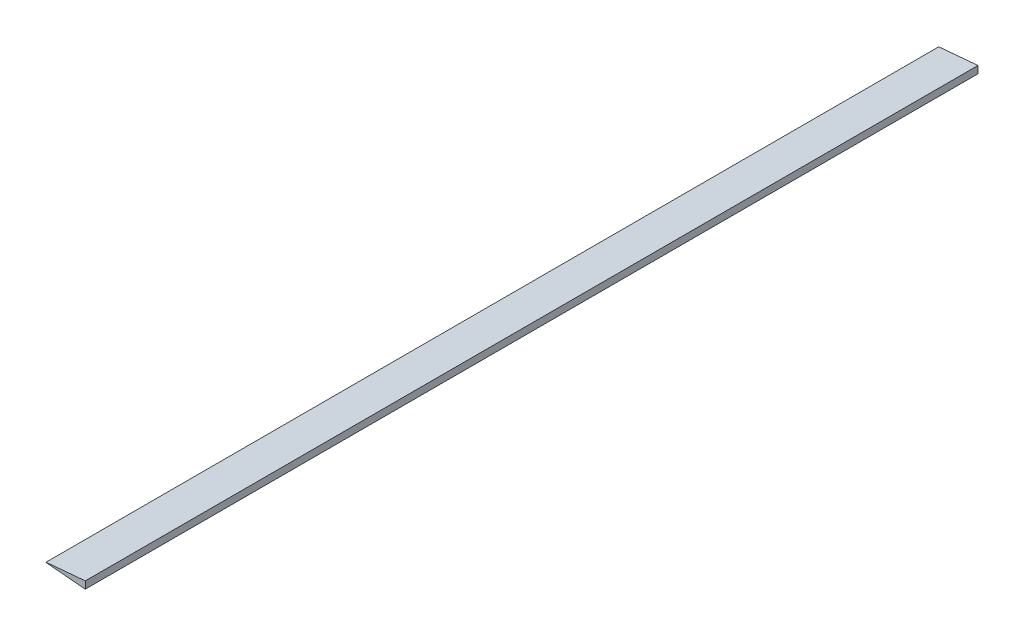
SolidWorks part; units mm, degrees
ref_plane "Front Plane" through (0, 0, 0) normal (0, 0, 1) x (1, 0, 0)
ref_plane "Top Plane" through (0, 0, 0) normal (0, 1, 0) x (1, 0, 0)
ref_plane "Right Plane" through (0, 0, 0) normal (1, 0, 0) x (0, 0, -1)
sketch "Sketch1" plane through (0, 0, 0) normal (0, 0, 1) x (1, 0, 0)
  line L0 (-86.8182, 3.4071) -> (-86.8182, -3.4071)
  line L1 (-124.026, 0.1172) -> (-124.026, -0.1172)
  spline S0 degree 3 poles (-86.8182, 3.4071) (-86.9575, 3.3973) (-89.0253, 3.2514) (-92.9071, 2.9508) (-98.3311, 2.5177) (-103.3571, 2.0925) (-107.93, 1.6883) (-111.9999, 1.3136) (-115.5222, 0.9774) (-118.4581, 0.6885) (-120.7757, 0.4545) (-122.4494, 0.2821) (-123.4611, 0.1766) (-123.9128, 0.1291) (-124.026, 0.1172) knots 0 0 0 0 0.011212 0.166483 0.312686 0.448211 0.571563 0.681381 0.776452 0.855723 0.918312 0.963525 0.990856 1 1 1 1
  spline S1 degree 3 poles (-86.8182, -3.4071) (-86.9575, -3.3973) (-89.0253, -3.2514) (-92.9071, -2.9508) (-98.3311, -2.5177) (-103.3571, -2.0925) (-107.93, -1.6883) (-111.9999, -1.3136) (-115.5222, -0.9774) (-118.4581, -0.6885) (-120.7757, -0.4545) (-122.4494, -0.2821) (-123.4611, -0.1766) (-123.9128, -0.1291) (-124.026, -0.1172) knots 0 0 0 0 0.011212 0.166483 0.312686 0.448211 0.571563 0.681381 0.776452 0.855723 0.918312 0.963525 0.990856 1 1 1 1
extrude "Boss-Extrude1" add sketch "Sketch1" along normal mid plane 845.8
